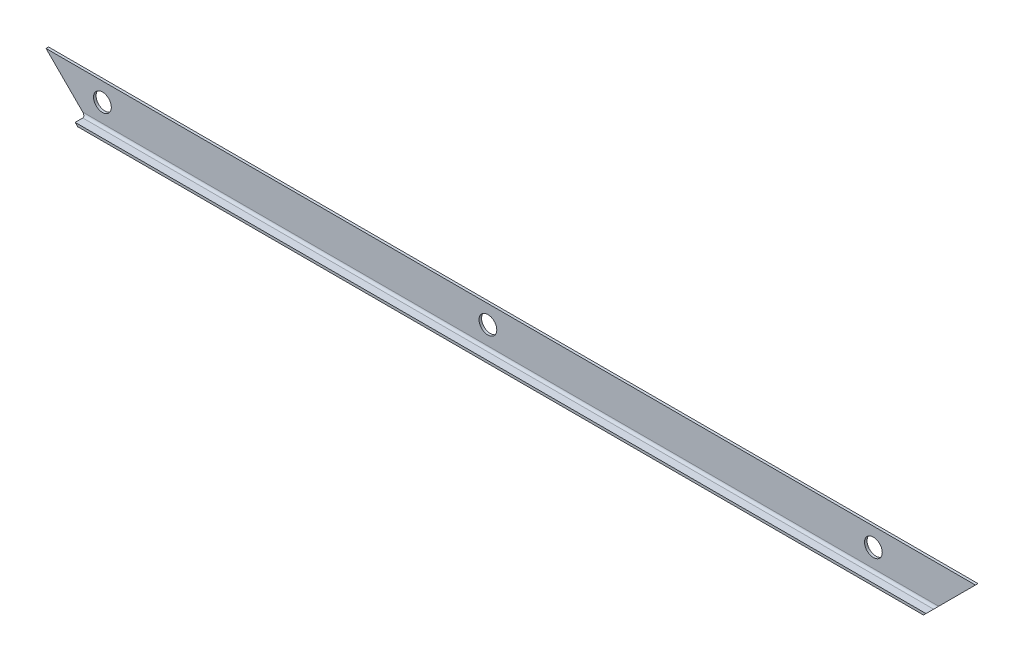
SolidWorks part; units mm, degrees
note: The reader was unsure of these and kept them because the rebuilt part matched: flange length of "Edge-Flange1".
material "Galvanized Steel"
ref_plane "Front Plane" through (0, 0, 0) normal (0, 0, 1) x (1, 0, 0)
ref_plane "Top Plane" through (0, 0, 0) normal (0, 1, 0) x (1, 0, 0)
ref_plane "Right Plane" through (0, 0, 0) normal (1, 0, 0) x (0, 0, -1)
sketch "Sketch1" plane through (0, 0, 0) normal (0, 0, 1) x (1, 0, 0)
  line L1 (-540, -16.5) -> (540, -16.5)
  line L2 (-540, -16.5) -> (-540, 16.5)
  line L3 (-540, 16.5) -> (540, 16.5)
  line L4 (540, -16.5) -> (540, 16.5)
  line L5 (-540, -16.5) -> (540, 16.5) construction
  line L6 (-540, 16.5) -> (540, -16.5) construction
  point P0 (0, 0)
base flange "Base-Flange1" sketch "Sketch1" thickness 2 reverse thickness direction no parameters "D1"=2
edge flange "Edge-Flange1" sketch "Sketch8" flange angle 90 flange length 10 flange position material inside bend radius 2 thickness 2 relief rectangular parameters "D6"=10
sketch "Sketch8" plane through (0, -16.5, 0) normal (0, -1, 0) x (1, 0, 0)
  line L0 (-540, 0) -> (540, 0) construction
  line L1 (-540, 0) -> (540, 0)
  line L2 (-540, 0) -> (-540, 8)
  line L3 (-540, 8) -> (540, 8)
  line L4 (540, 8) -> (540, 0)
bend "EdgeBend1" bend radius 2 bend angle 90 parameters "D5"=1
sketch "Sketch9" plane through (0, 0, 0) normal (0, 0, 1) x (1, 0, 0)
  circle A0 centre (-930, 2) radius 7
  circle A1 centre (-626, 2) radius 7
  circle A2 centre (-322, 2) radius 7
  circle A3 centre (-18, 2) radius 7
  circle A4 centre (286, 2) radius 7
  circle A5 centre (590, 2) radius 7
  circle A6 centre (894, 2) radius 7
  dimension "D1" = 7
  dimension "D2" = 304
extrude "Cut-Extrude1" cut sketch "Sketch9" against normal blind 10
sketch "Sketch10" plane through (0, 0, 0) normal (0, 0, 1) x (1, 0, 0)
  line L1 (-302.3774, -47.6226) -> (-401.6226, 51.6226)
  line L2 (-401.6226, 51.6226) -> (-590.4179, 51.6226)
  line L3 (-590.4179, 51.6226) -> (-583.6536, -79.0568)
  line L4 (-583.6536, -79.0568) -> (-558.626, -79.0568)
  line L5 (-558.626, -79.0568) -> (-302.3774, -47.6226)
  line L6 (558.626, -79.0568) -> (302.3774, -47.6226)
  line L7 (583.6536, -79.0568) -> (558.626, -79.0568)
  line L8 (590.4179, 51.6226) -> (583.6536, -79.0568)
  line L9 (401.6226, 51.6226) -> (590.4179, 51.6226)
  line L10 (302.3774, -47.6226) -> (401.6226, 51.6226)
  point P6 (-352, 2)
  point P15 (352, 2)
extrude "Cut-Extrude2" cut sketch "Sketch10" against normal blind 40 and the other way blind 40
sketch "Bend-Lines1" [suppressed] plane through (0, 0, 0) normal (0, 1, 0) x (1, 0, 0)
sketch "Bounding-Box1" [suppressed] plane through (0, 0, 0) normal (0, 1, 0) x (1, 0, 0)
sheet metal parameters "Sheet-Metal1" thickness 2 parameters "D1"=2
flat pattern "Flat-Pattern1" [suppressed]
sketch "Bend-Lines2" plane through (0, 0, 0) normal (0, 1, 0) x (1, 0, 0)
sketch3d "Bounding-Box2" [suppressed]
  line L0 (108, -16.5, 0) -> (-108, -16.5, 0) construction
  line L1 (108, 16.5, 0) -> (-108, 16.5, 0) construction
  line L2 (108, -16.5, 0) -> (108, 16.5, 0) construction
  line L3 (-108, -16.5, 0) -> (-108, 16.5, 0) construction
sheet metal parameters "Sheet-Metal2" thickness 2 parameters "D1"=2
flat pattern "Flat-Pattern1"
sketch "Bend-Lines2" plane through (0, 0, 0) normal (0, 0, 1) x (1, 0, 0)
  line L0 (-1080, -14.8562) -> (1080, -14.8562) construction
  line L1 (-1080, -14.8562) -> (1080, -14.8562) construction
sketch3d "Bounding-Box2" [suppressed]
  line L0 (-1080, -23.2124, 0) -> (1080, -23.2124, 0) construction
  line L1 (-1080, 16.5, 0) -> (1080, 16.5, 0) construction
  line L2 (-1080, -23.2124, 0) -> (-1080, 16.5, 0) construction
  line L3 (1080, -23.2124, 0) -> (1080, 16.5, 0) construction
bend of the flat pattern "Flatten-<EdgeBend1>1"
sheet metal parameters "Sheet-Metal3" thickness 2 parameters "D1"=2
flat pattern "Flat-Pattern1"
sketch "Bend-Lines2" plane through (0, 0, 0) normal (0, 0, 1) x (1, 0, 0)
  line L0 (-540, -14.8562) -> (540, -14.8562) construction
  line L1 (-540, -14.8562) -> (540, -14.8562) construction
sketch3d "Bounding-Box2" [suppressed]
  line L0 (-540, -23.2124, 0) -> (540, -23.2124, 0) construction
  line L1 (-540, 16.5, 0) -> (540, 16.5, 0) construction
  line L2 (-540, -23.2124, 0) -> (-540, 16.5, 0) construction
  line L3 (540, -23.2124, 0) -> (540, 16.5, 0) construction
bend of the flat pattern "Flatten-<EdgeBend1>1"
sheet metal parameters "Sheet-Metal4" thickness 2 parameters "D1"=2
flat pattern "Flat-Pattern1"
sketch "Bend-Lines2" plane through (0, 0, 0) normal (0, 0, 1) x (1, 0, 0)
  line L0 (-337.5, -14.8562) -> (335.5, -14.8562) construction
  line L1 (-337.5, -14.8562) -> (335.5, -14.8562) construction
sketch3d "Bounding-Box2" [suppressed]
  line L0 (-366.5, -23.2124, 0) -> (366.5, -23.2124, 0) construction
  line L1 (-366.5, 16.5, 0) -> (366.5, 16.5, 0) construction
  line L2 (-366.5, -23.2124, 0) -> (-366.5, 16.5, 0) construction
  line L3 (366.5, -23.2124, 0) -> (366.5, 16.5, 0) construction
bend of the flat pattern "Flatten-<EdgeBend1>1"
